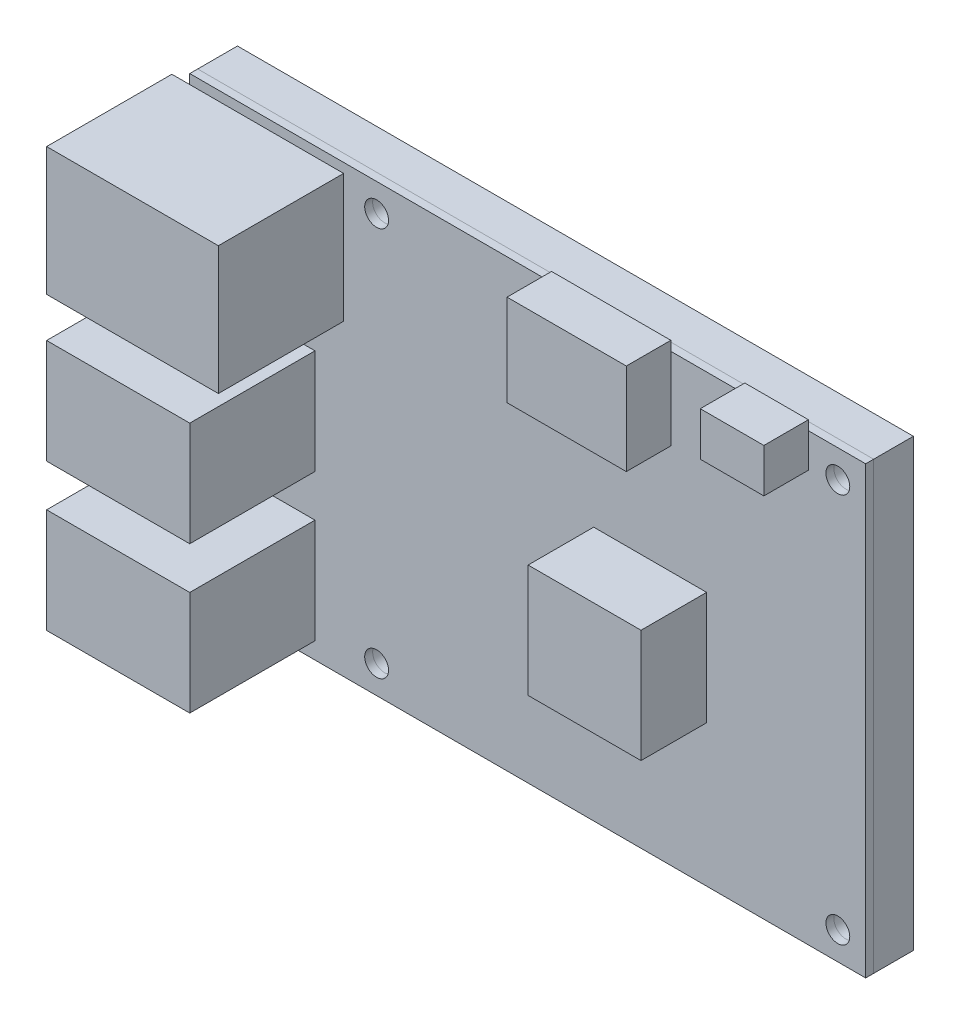
SolidWorks part; units mm, degrees
ref_plane "Front Plane" through (0, 0, 0) normal (0, 0, 1) x (1, 0, 0)
ref_plane "Top Plane" through (0, 0, 0) normal (0, 1, 0) x (1, 0, 0)
ref_plane "Right Plane" through (0, 0, 0) normal (1, 0, 0) x (0, 0, -1)
sketch "Sketch1" plane through (0, 0, 0) normal (0, 0, 1) x (1, 0, 0)
  line L0 (-12.9184, 34.1475) -> (45.0816, 34.1475) construction
  line L1 (-36.4184, 37.6475) -> (48.5816, 37.6475)
  line L2 (-36.4184, 37.6475) -> (-36.4184, -18.3525)
  line L3 (-36.4184, -18.3525) -> (48.5816, -18.3525)
  line L4 (48.5816, 37.6475) -> (48.5816, -18.3525)
  line L5 (45.0816, 34.1475) -> (45.0816, -14.8525) construction
  line L6 (45.0816, -14.8525) -> (-12.9184, -14.8525) construction
  line L7 (-12.9184, -14.8525) -> (-12.9184, 34.1475) construction
  line L8 (45.0816, 9.6475) -> (48.5816, 9.6475) construction
  circle A0 centre (-12.9184, 34.1475) radius 1.5
  circle A1 centre (-12.9184, -14.8525) radius 1.5
  circle A2 centre (45.0816, 34.1475) radius 1.5
  circle A3 centre (45.0816, -14.8525) radius 1.5
  dimension "D1" = 3
  dimension "D2" = 58
  dimension "D3" = 49
  dimension "D4" = 56
  dimension "D5" = 85
  dimension "D6" = 3.5
extrude "Boss-Extrude1" add sketch "Sketch1" along normal blind 1
extrude "Boss-Extrude2" add sketch "Sketch1<2>" against normal blind 5 separate body
sketch "Sketch1<2>" plane through (0, 0, 0) normal (0, 0, 1) x (1, 0, 0) same geometry as "Sketch1"
sketch "Sketch3" plane through (0, 0, 1) normal (0, 0, 1) x (1, 0, 0)
  line L0 (48.5816, 37.6475) -> (48.5816, -18.3525) construction
  line L1 (14.3816, 13.6475) -> (28.5816, 13.6475)
  line L2 (14.3816, 13.6475) -> (14.3816, -0.5525)
  line L3 (14.3816, -0.5525) -> (28.5816, -0.5525)
  line L4 (28.5816, 13.6475) -> (28.5816, -0.5525)
  line L5 (-36.4184, 37.6475) -> (48.5816, 37.6475) construction
  dimension "D1" = 14.2
  dimension "D2" = 14.2
  dimension "D3" = 20
  dimension "D4" = 24
extrude "Boss-Extrude3" add sketch "Sketch3" along normal blind 8.25
sketch "Sketch4" plane through (0, 0, 1) normal (0, 0, 1) x (1, 0, 0)
  line L0 (-38.6679, 8.7575) -> (-28.6679, 8.7575) construction
  line L1 (-38.6679, 15.3275) -> (-20.6679, 15.3275)
  line L2 (-38.6679, 15.3275) -> (-38.6679, 2.1875)
  line L3 (-38.6679, 2.1875) -> (-20.6679, 2.1875)
  line L4 (-20.6679, 15.3275) -> (-20.6679, 2.1875)
  line L5 (-38.6679, -3.1125) -> (-20.6679, -3.1125)
  line L6 (-38.6679, -3.1125) -> (-38.6679, -16.2525)
  line L7 (-38.6679, -16.2525) -> (-20.6679, -16.2525)
  line L8 (-20.6679, -3.1125) -> (-20.6679, -16.2525)
  line L9 (-38.6679, -9.6825) -> (-28.6679, -9.6825) construction
  line L12 (-38.6679, 36.4475) -> (-17.0679, 36.4475)
  line L13 (-38.6679, 36.4475) -> (-38.6679, 20.3475)
  line L14 (-38.6679, 20.3475) -> (-17.0679, 20.3475)
  line L15 (-17.0679, 36.4475) -> (-17.0679, 20.3475)
  dimension "D1" = 18
  dimension "D2" = 13.14
  dimension "D3" = 10
  dimension "D4" = 5.3
  dimension "D5" = 2.1
  dimension "D6" = 21.6
  dimension "D7" = 1.2
  dimension "D8" = 16.1
extrude "Boss-Extrude4" add sketch "Sketch4" along normal blind 15.75
sketch "Sketch5" plane through (0, 0, 1) normal (0, 0, 1) x (1, 0, 0)
  line L1 (9.0816, 38.8475) -> (24.0816, 38.8475)
  line L2 (9.0816, 38.8475) -> (9.0816, 27.3475)
  line L3 (9.0816, 27.3475) -> (24.0816, 27.3475)
  line L4 (24.0816, 38.8475) -> (24.0816, 27.3475)
  line L5 (33.3816, 38.8475) -> (41.3816, 38.8475)
  line L6 (33.3816, 38.8475) -> (33.3816, 33.3475)
  line L7 (33.3816, 33.3475) -> (41.3816, 33.3475)
  line L8 (41.3816, 38.8475) -> (41.3816, 33.3475)
  dimension "D1" = 15
  dimension "D2" = 8
  dimension "D3" = 11.5
  dimension "D4" = 5.5
  dimension "D5" = 1.2
  dimension "D6" = 24.5
  dimension "D7" = 7.2
extrude "Boss-Extrude5" add sketch "Sketch5" along normal blind 5.6
